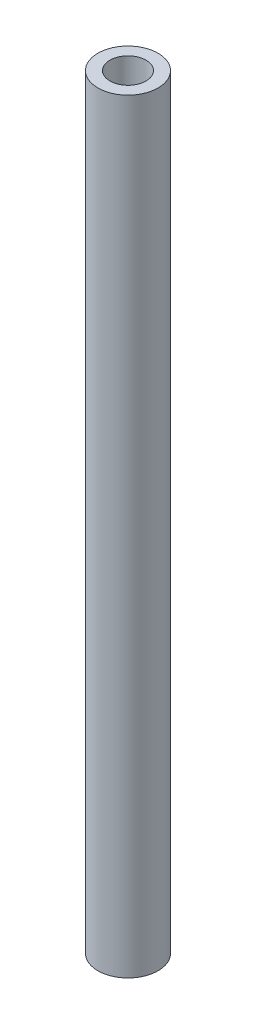
SolidWorks part; units mm, degrees
material "6061-T6 (SS)"
ref_plane "Front Plane" through (0, 0, 0) normal (0, 0, 1) x (1, 0, 0)
ref_plane "Top Plane" through (0, 0, 0) normal (0, 1, 0) x (1, 0, 0)
ref_plane "Right Plane" through (0, 0, 0) normal (1, 0, 0) x (0, 0, -1)
sketch "Sketch1" plane through (0, 0, 0) normal (0, 1, 0) x (1, 0, 0)
  circle A0 centre (0, 0) radius 3.5
  dimension "D1" = 7
extrude "Boss-Extrude1" add sketch "Sketch1" along normal blind 88.9
hole_wizard "Tap Drill for M5x0.8 Tap1" positions "Sketch3" profile "Sketch4" hole size "M5x0.8" standard "ANSI Metric"
sketch "Sketch3" plane through (0, 88.9, 0) normal (0, 1, 0) x (1, 0, 0)
  point P0 (0, 0)
sketch "Sketch4" plane through (0, 88.9, 0) normal (1, 0, 0) x (0, 0, 1)
  line L0 (0, 0) -> (0, 26.2618)
  line L1 (0, 26.2618) -> (2.1, 25)
  line L2 (2.1, 25) -> (2.1, 0)
  line L5 (2.1, 0) -> (0, 0)
  line L10 (0, 26.2618) -> (-2.1, 25) construction
  line L11 (0, -6.35) -> (0, 107.95) construction
  dimension "Hole Dia." = 4.2
  dimension "Hole Depth" = 25
  dimension "Drill Angle" = 118
hole_wizard "Tap Drill for M5x0.8 Tap2" positions "Sketch5" profile "Sketch6" hole size "M5x0.8" standard "ANSI Metric"
sketch "Sketch5" plane through (0, 0, 0) normal (0, -1, 0) x (-1, 0, 0)
  point P0 (0, 0)
sketch "Sketch6" plane through (0, 0, 0) normal (1, 0, 0) x (0, 0, -1)
  line L0 (0, 0) -> (0, 26.1538)
  line L1 (0, 26.1538) -> (2.1, 24.892)
  line L2 (2.1, 24.892) -> (2.1, 0)
  line L5 (2.1, 0) -> (0, 0)
  line L10 (0, 26.1538) -> (-2.1, 24.892) construction
  line L11 (0, -6.35) -> (0, 107.95) construction
  dimension "Hole Dia." = 4.2
  dimension "Hole Depth" = 24.892
  dimension "Drill Angle" = 118
